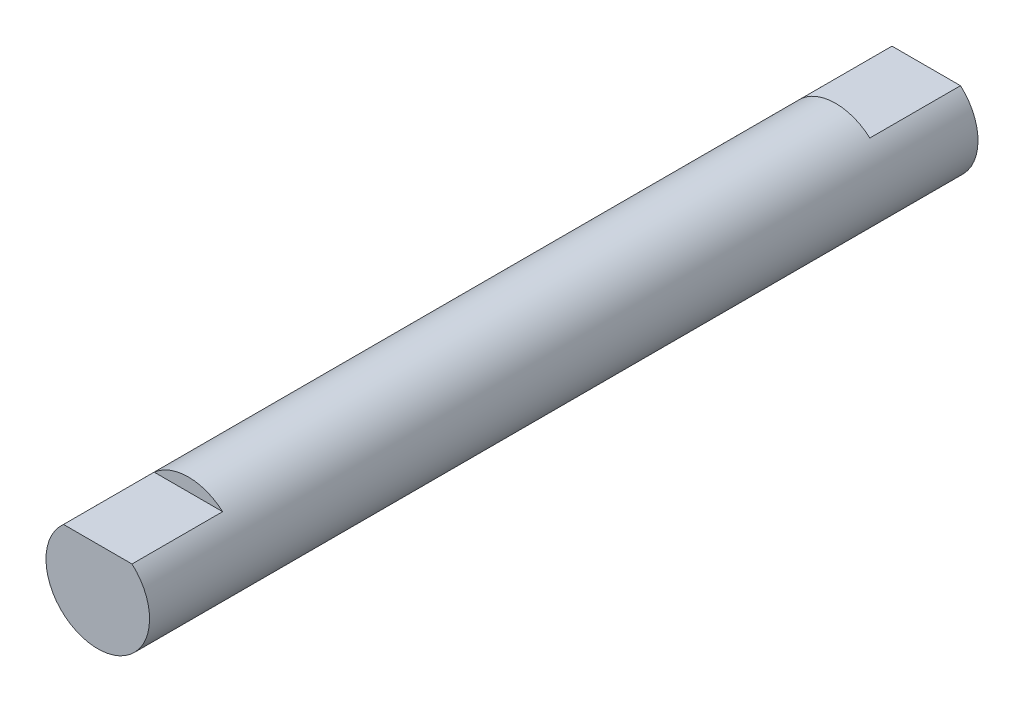
SolidWorks part; units mm, degrees
material "Steel Rod"
ref_plane "Front Plane" through (0, 0, 0) normal (0, 0, 1) x (1, 0, 0)
ref_plane "Top Plane" through (0, 0, 0) normal (0, 1, 0) x (1, 0, 0)
ref_plane "Right Plane" through (0, 0, 0) normal (1, 0, 0) x (0, 0, -1)
ref_plane "End1" through (0, 0, 50.8) normal (0, 0, 1) x (1, 0, 0)
ref_plane "End2" through (0, 0, -50.8) normal (0, 0, 1) x (1, 0, 0)
sketch "Sketch1" plane through (0, 0, 0) normal (0, 0, 1) x (1, 0, 0)
  circle A0 centre (0, 0) radius 6.35
  dimension "D1" = 12.7
extrude "Basic Rod" add sketch "Sketch1" along normal up to surface (50.8 mm away) and the other way up to surface (50.8 mm away) up to plane "End1" other way up to plane "End2"
ref_axis "Center Axis" through (0, 0, -35.4838) along (0, 0, 1)
sketch "Sketch8" plane through (0, 0, 0) normal (0, 0, 1) x (1, 0, 0)
  line L0 (-5.4616, 4.1791) -> (-6.35, 3.6662) construction
  line L1 (-0.8884, 6.8194) -> (-5.4616, 4.1791)
  line L2 (-6.35, 2.6403) -> (-6.35, -2.6403)
  line L3 (-5.4616, -4.1791) -> (-0.8884, -6.8194)
  line L4 (0.8884, -6.8194) -> (5.4616, -4.1791)
  line L5 (6.35, -2.6403) -> (6.35, 2.6403)
  line L6 (5.4616, 4.1791) -> (0.8884, 6.8194)
  line L7 (-6.35, 3.6662) -> (-6.35, 2.6403) construction
  line L8 (0, 7.3323) -> (-0.8884, 6.8194) construction
  line L9 (0.8884, 6.8194) -> (0, 7.3323) construction
  line L10 (6.35, 3.6662) -> (5.4616, 4.1791) construction
  line L11 (6.35, 2.6403) -> (6.35, 3.6662) construction
  line L12 (6.35, -3.6662) -> (6.35, -2.6403) construction
  line L13 (5.4616, -4.1791) -> (6.35, -3.6662) construction
  line L14 (0, -7.3323) -> (0.8884, -6.8194) construction
  line L15 (-0.8884, -6.8194) -> (0, -7.3323) construction
  line L16 (-6.35, -3.6662) -> (-5.4616, -4.1791) construction
  line L17 (-6.35, -2.6403) -> (-6.35, -3.6662) construction
  circle A0 centre (0, 0) radius 6.35 construction
  arc A1 (-6.35, -2.6403) -> (-5.4616, -4.1791) centre (0, 0) ccw
  circle A2 centre (0, 0) radius 6.35 construction
  arc A3 (-6.35, 2.6403) -> (-6.35, -2.6403) centre (0, 0) ccw construction
  arc A4 (-0.8884, 6.8194) -> (-5.4616, 4.1791) centre (0, 0) ccw construction
  arc A5 (-5.4616, 4.1791) -> (-6.35, 2.6403) centre (0, 0) ccw
  arc A6 (5.4616, 4.1791) -> (0.8884, 6.8194) centre (0, 0) ccw construction
  arc A7 (0.8884, 6.8194) -> (-0.8884, 6.8194) centre (0, 0) ccw
  arc A8 (6.35, -2.6403) -> (6.35, 2.6403) centre (0, 0) ccw construction
  arc A9 (6.35, 2.6403) -> (5.4616, 4.1791) centre (0, 0) ccw
  arc A10 (0.8884, -6.8194) -> (5.4616, -4.1791) centre (0, 0) ccw construction
  arc A11 (5.4616, -4.1791) -> (6.35, -2.6403) centre (0, 0) ccw
  arc A12 (-5.4616, -4.1791) -> (-0.8884, -6.8194) centre (0, 0) ccw construction
  arc A13 (-0.8884, -6.8194) -> (0.8884, -6.8194) centre (0, 0) ccw
  dimension "D1" = 13.7541
extrude "THex" [suppressed] add sketch "Sketch8" along normal mid plane 101.6
sketch "Sketch5" plane through (0, 0, 0) normal (0, 0, 1) x (1, 0, 0)
  line L1 (-3.6662, 6.35) -> (-7.3323, 0)
  line L2 (-7.3323, 0) -> (-3.6662, -6.35)
  line L3 (-3.6662, -6.35) -> (3.6662, -6.35)
  line L4 (3.6662, -6.35) -> (7.3323, 0)
  line L5 (7.3323, 0) -> (3.6662, 6.35)
  line L6 (3.6662, 6.35) -> (-3.6662, 6.35)
  circle A0 centre (0, 0) radius 6.35 construction
  circle A2 centre (0, 0) radius 6.35 construction
extrude "Hex" [suppressed] add sketch "Sketch5" along normal mid plane 101.6
sketch "Sketch7" plane through (0, 0, 0) normal (1, 0, 0) x (0, 0, -1)
  line L0 (0, 0) -> (-50000, 0) construction
  line L1 (-50.8, 5.9436) -> (-51.816, 5.9436)
  line L2 (-51.816, 5.9436) -> (-51.816, 6.35)
  line L3 (-51.816, 6.35) -> (-52.832, 6.35)
  line L4 (-53.34, 5.842) -> (-53.34, 0)
  line L5 (-53.34, 0) -> (-50.8, 0)
  line L6 (-50.8, 0) -> (-50.8, 5.9436)
  line L7 (-52.832, 6.35) -> (-53.34, 5.842)
  line L8 (35.4838, 0) -> (-35.4838, 0) construction
  line L9 (-50.8, 5.2388) -> (-50.8, -5.2388) construction
  point P7 (-53.34, 6.35)
  dimension "D1" = 12.7
  dimension "D4" = 1.016
  dimension "D2" = 0.4064
  dimension "D3" = 2.54
revolve "1stSnapRing" [suppressed] add sketch "Sketch7" angle 360 about axis through (0, 0, -35.4838) along (0, 0, 1)
mirror "2ndSnapRing" [suppressed] about plane through (0, 0, 0) normal (0, 0, 1)
sketch "Sketch2" plane through (0, 0, 0) normal (0, 0, 1) x (1, 0, 0)
  circle A0 centre (0, 0) radius 2.5527
  dimension "D1" = 5.1054
extrude "Internal Cut" [suppressed] cut sketch "Sketch2" against normal through all both and the other way through all
sketch "Sketch9" plane through (0, 0, 0) normal (0, 1, 0) x (1, 0, 0)
  line L0 (-6.35, -50.8) -> (6.35, -50.8) construction
  line L1 (-6.35, -50.8) -> (6.35, -50.8)
  line L2 (6.35, 50.8) -> (-6.35, 50.8) construction
  line L3 (6.35, 50.8) -> (-6.35, 50.8)
  line L4 (6.35, -50.8) -> (6.35, 50.8) construction
  line L5 (-6.35, -50.8) -> (6.35, -50.8)
  line L6 (-6.35, -50.8) -> (-6.35, -39.6875)
  line L7 (-6.35, -39.6875) -> (6.35, -39.6875)
  line L8 (6.35, -50.8) -> (6.35, -39.6875)
  line L10 (-6.35, 50.8) -> (6.35, 50.8)
  line L11 (-6.35, 50.8) -> (-6.35, 39.6875)
  line L12 (-6.35, 39.6875) -> (6.35, 39.6875)
  line L13 (6.35, 50.8) -> (6.35, 39.6875)
  dimension "D1" = 11.1125
extrude "Cut-Extrude1" cut sketch "Sketch9" along normal through all from offset 4.7625 contours L1 L8 L7 L6 | L13 L3 L11 L12 region at (0, 0, 45.2437) region at (0, 0, -45.2437)
equation "\"Unit Measure\"= \"Length\"'in"
equation "\"D1@Sketch1\"=\"OD\""
equation "\"D1\"= \"Length\""
equation "\"D1@Sketch2\"=\"ID\""
equation "\"Internal Cut\"= IIF ( \"ID\" = 0 ,  suppressed  ,  unsuppressed  ) "
equation "\"D1@Hex\" = \"Length\""
equation "\"Hex\" = IIF ( \"SelectionType\" = 1 , \"suppressed\" , iif ( \"SelectionType\" = 2 , \"suppressed\" , \"unsuppressed\" ) )"
equation "\"OutsideDiameter\"= \"OD\"'in"
equation "\"ThunderHexDia\"= iif ( \"OD\" < .36 , \"OD\" * 1.1 , iif ( \"OD\" < .40 , .4035 , iif ( \"OD\" < .52 , .5415 , \"OD\" * 1.1 ) ) )"
equation "\"D1@Sketch7\"=\"Thickness\""
equation "\"SRDia\"= iif ( \"OD\" = .5 , ( \"OD\" - .468 ) / 2 , iif ( \"OD\" = .375 , ( \"OD\" - .352 ) / 2 , .050 ) )"
equation "\"D2@Sketch7\"= \"SnapRingDepth\""
equation "\"1stSnapRing\"= iif ( \"SnapRingCount\" > 0 , \"unsuppressed\" , \"suppressed\" )"
equation "\"2ndSnapRing\"= iif ( \"SnapRingCount\" = 2 , \"unsuppressed\" , \"suppressed\" )"
equation "\"D1@End1\" = \"Length\" / 2"
equation "\"D1@End2\" = \"Length\""
equation "\"D1@Sketch8\"=\"ThunderHexDia\""
equation "\"D1@THex\" = \"Length\""
equation "\"THex\"= IIF ( \"SelectionType\" = 0 ,  suppressed  , iif ( \"SelectionType\" = 2 ,  suppressed  ,  unsuppressed  )  ) "
